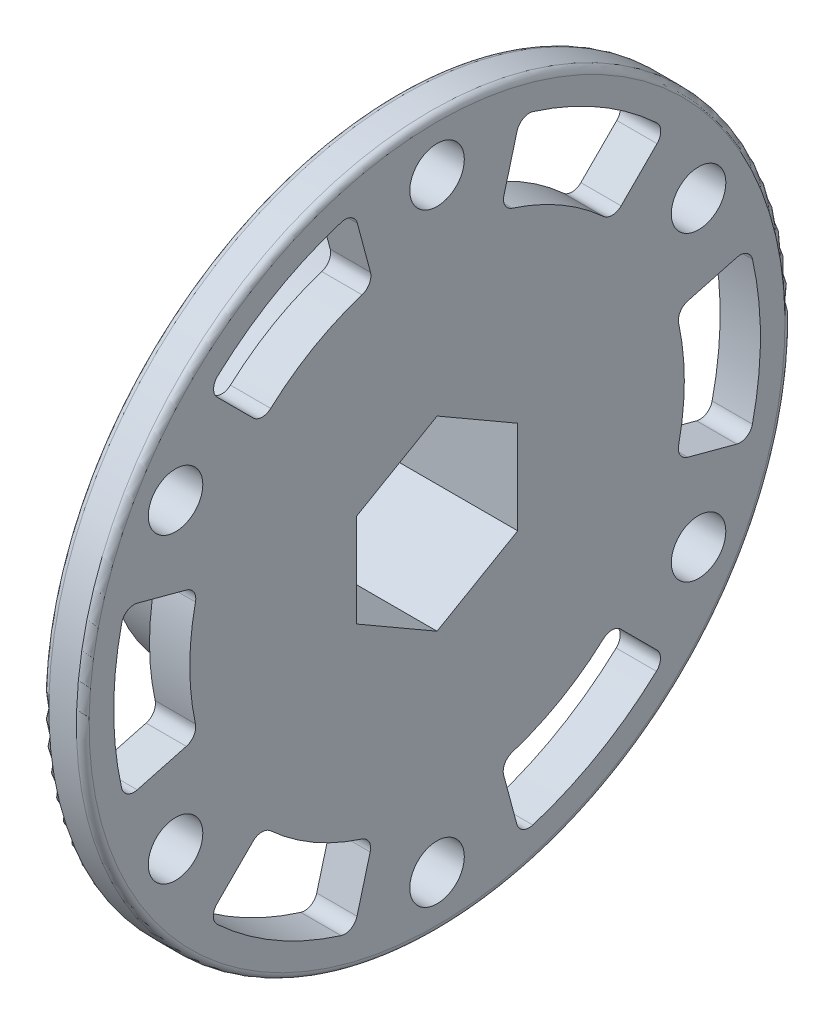
SolidWorks part; units mm, degrees
ref_plane "Front Plane" through (0, 0, 0) normal (0, 0, 1) x (1, 0, 0)
ref_plane "Top Plane" through (0, 0, 0) normal (0, 1, 0) x (1, 0, 0)
ref_plane "Right Plane" through (0, 0, 0) normal (1, 0, 0) x (0, 0, -1)
ref_plane "Plane1" through (0, 0, 0) normal (0, 0, -1) x (-1, 0, 0)
sketch "Sketch1" plane through (0, 0, 0) normal (0, 0, -1) x (-1, 0, 0)
  line L0 (-12.7, 27.94) -> (-12.7, 0)
  line L1 (-12.7, 0) -> (-9.525, 0)
  line L2 (-9.525, 0) -> (-9.525, 27.94)
  line L3 (-9.525, 27.94) -> (-12.7, 27.94)
  line L4 (-12.7, 0) -> (-9.525, 0) construction
revolve "Revolve1" add sketch "Sketch1" angle 360 about L4 reverse direction yes
sketch "Sketch2" plane through (9.525, 0, 0) normal (-1, 0, 0) x (0, 0, 1)
  line L0 (-13.8065, -13.7706) -> (-18.0492, -18.0133)
  line L1 (-6.5508, -24.6442) -> (-4.9979, -18.8486)
  arc A0 (-4.9979, -18.8486) -> (-13.8065, -13.7706) centre (0, 0) cw
  arc A1 (-18.0492, -18.0133) -> (-6.5508, -24.6442) centre (0, 0) ccw
extrude "Cut-Extrude1" cut sketch "Sketch2" against normal through all
sketch "Sketch3" plane through (9.525, 0, 0) normal (-1, 0, 0) x (0, 0, 1)
  line L0 (5.0224, -18.8421) -> (6.5753, -24.6377)
  line L1 (18.0671, -17.9953) -> (13.8245, -13.7526)
  arc A0 (13.8245, -13.7526) -> (5.0224, -18.8421) centre (0, 0) cw
  arc A1 (6.5753, -24.6377) -> (18.0671, -17.9953) centre (0, 0) ccw
extrude "Cut-Extrude2" cut sketch "Sketch3" against normal through all
sketch "Sketch4" plane through (9.525, 0, 0) normal (-1, 0, 0) x (0, 0, 1)
  line L0 (18.829, -5.0715) -> (24.6245, -6.6244)
  line L1 (24.6179, 6.6489) -> (18.8223, 5.096)
  arc A0 (18.8223, 5.096) -> (18.829, -5.0715) centre (0, 0) cw
  arc A1 (24.6245, -6.6244) -> (24.6179, 6.6489) centre (0, 0) ccw
extrude "Cut-Extrude3" cut sketch "Sketch4" against normal through all
sketch "Sketch5" plane through (9.525, 0, 0) normal (-1, 0, 0) x (0, 0, 1)
  line L0 (13.8065, 13.7706) -> (18.0492, 18.0133)
  line L1 (6.5508, 24.6442) -> (4.9979, 18.8486)
  arc A0 (4.9979, 18.8486) -> (13.8065, 13.7706) centre (0, 0) cw
  arc A1 (18.0492, 18.0133) -> (6.5508, 24.6442) centre (0, 0) ccw
extrude "Cut-Extrude4" cut sketch "Sketch5" against normal through all
sketch "Sketch6" plane through (9.525, 0, 0) normal (-1, 0, 0) x (0, 0, 1)
  line L0 (-24.6179, -6.6489) -> (-18.8223, -5.096)
  line L1 (-18.829, 5.0715) -> (-24.6245, 6.6244)
  arc A0 (-18.8223, -5.096) -> (-18.829, 5.0715) centre (0, 0) cw
  arc A1 (-24.6245, 6.6244) -> (-24.6179, -6.6489) centre (0, 0) ccw
extrude "Cut-Extrude5" cut sketch "Sketch6" against normal through all
sketch "Sketch7" plane through (12.7, 0, 0) normal (1, 0, 0) x (0, 0, -1)
  line L0 (6.5753, 24.6377) -> (5.0224, 18.8421)
  line L1 (13.8245, 13.7526) -> (18.0671, 17.9953)
  arc A0 (18.0671, 17.9953) -> (6.5753, 24.6377) centre (0, 0) ccw
  arc A1 (5.0224, 18.8421) -> (13.8245, 13.7526) centre (0, 0) cw
extrude "Cut-Extrude6" cut sketch "Sketch7" against normal through all
sketch "Sketch8" plane through (9.525, 0, 0) normal (-1, 0, 0) x (0, 0, 1)
  circle A0 centre (0, 0) radius 14.2949
extrude "Boss-Extrude1" add sketch "Sketch8" along normal blind 9.525
sketch "Sketch9" plane through (12.7, 0, 0) normal (1, 0, 0) x (0, 0, -1)
  line L0 (-6.3627, 3.6735) -> (-6.3627, -3.6735)
  line L1 (-6.3627, -3.6735) -> (0, -7.347)
  line L2 (0, -7.347) -> (6.3627, -3.6735)
  line L3 (6.3627, -3.6735) -> (6.3627, 3.6735)
  line L4 (6.3627, 3.6735) -> (0, 7.347)
  line L5 (0, 7.347) -> (-6.3627, 3.6735)
extrude "Cut-Extrude7" cut sketch "Sketch9" against normal through all
hole_wizard "#6 Clearance Hole1" positions "Sketch11" profile "Sketch10" hole size "#6" standard "ANSI Inch"
sketch "Sketch11" plane through (12.7, 0, 0) normal (1, 0, 0) x (0, 0, -1)
  point P0 (20.6222, 11.9063)
  point P1 (20.6222, -11.9062)
  point P2 (0, -23.8125)
  point P3 (-20.6222, -11.9063)
  point P4 (-20.6222, 11.9062)
  point P5 (0, 23.8125)
sketch "Sketch10" plane through (12.7, 11.9063, -20.6222) normal (0, 1, 0) x (0, 0, -1)
  line L0 (0, 0) -> (0, 12.7)
  line L1 (0, 12.7) -> (2.15, 12.7)
  line L2 (2.15, 12.7) -> (2.15, 0)
  line L5 (2.15, 0) -> (0, 0)
  line L11 (0, -6.35) -> (0, 107.95) construction
  dimension "Thru Hole Dia." = 4.3
  dimension "Thru Hole Depth" = 12.7
chamfer "Chamfer1" distance 1 angle 45 1 edges at (0, -14.2949, 0)
fillet "Fillet1" radius 0.5 2 edges at (12.7, -27.94, 0) (9.525, -27.94, 0) tangent propagation no
fillet "Fillet2" radius 1 24 edges at (11.1125, 6.6489, 24.6179) (11.1125, -17.9953, 18.0671) (11.1125, 24.6442, 6.5508) (11.1125, -18.8421, 5.0224) (11.1125, 18.8421, -5.0224) (11.1125, -5.0715, 18.829) (11.1125, 24.6377, -6.5753) (11.1125, 13.7706, 13.8065) (11.1125, 17.9953, -18.0671) (11.1125, -18.8486, -4.9979) (11.1125, 13.7526, -13.8245) (11.1125, -24.6377, 6.5753) (11.1125, 5.0715, -18.829) (11.1125, -13.7526, 13.8245) (11.1125, 6.6244, -24.6245) (11.1125, -6.6244, 24.6245) (11.1125, -6.6489, -24.6179) (11.1125, 5.096, 18.8223) (11.1125, -5.096, -18.8223) (11.1125, 18.0133, 18.0492) (11.1125, -13.7706, -13.8065) (11.1125, 18.8486, 4.9979) (11.1125, -18.0133, -18.0492) (11.1125, -24.6442, -6.5508) tangent propagation no
fillet "Fillet3" radius 1.27 1 edges at (9.525, -14.2949, 0) tangent propagation no
ref_axis "Axis1" through (13.335, 0, 0) along (-1, 0, 0)
ref_axis "Axis2" through (9.525, 11.9063, -20.6222) along (1, 0, 0)
ref_axis "Axis3" through (9.525, -11.9062, -20.6222) along (1, 0, 0)
ref_axis "Axis4" through (9.525, -23.8125, 0) along (1, 0, 0)
ref_axis "Axis5" through (9.525, -11.9063, 20.6222) along (1, 0, 0)
ref_axis "Axis6" through (9.525, 11.9062, 20.6222) along (1, 0, 0)
ref_axis "Axis7" through (9.525, 23.8125, 0) along (1, 0, 0)
